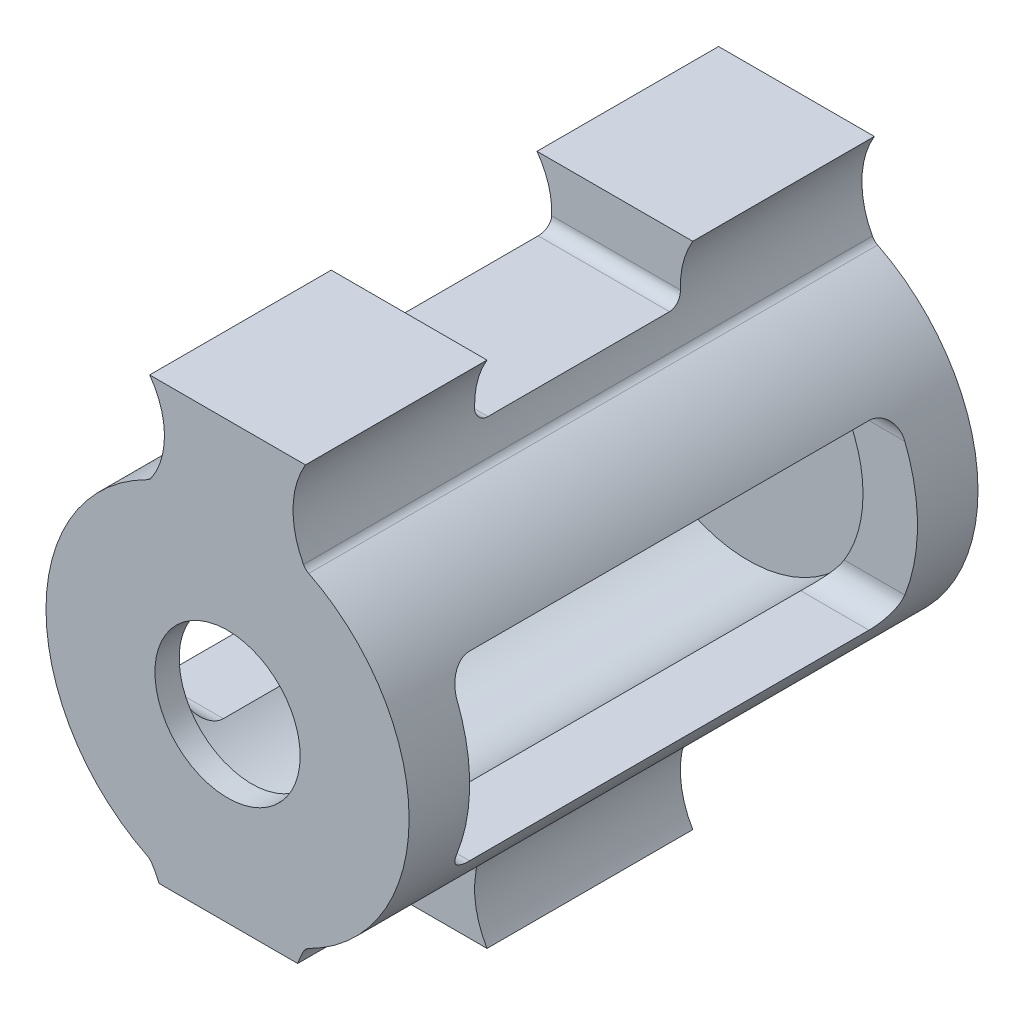
SolidWorks part; units mm, degrees
material "AISI 4130 Steel, annealed at 865C"
ref_plane "Front Plane" through (0, 0, 0) normal (0, 0, 1) x (1, 0, 0)
ref_plane "Top Plane" through (0, 0, 0) normal (0, 1, 0) x (1, 0, 0)
ref_plane "Right Plane" through (0, 0, 0) normal (1, 0, 0) x (0, 0, -1)
other "Center of Mass"
sketch "Sketch1" plane through (0, 0, 0) normal (0, 0, 1) x (1, 0, 0)
  line L8 (-38.1, 0) -> (-52.5688, 0)
  line L9 (-16.3476, 53.4646) -> (16.3476, 53.4646)
  line L10 (-16.3476, -53.4646) -> (16.3476, -53.4646)
  circle A0 centre (0, 0) radius 38.1
  circle A1 centre (0, 0) radius 26.67
  arc A2 (-16.3476, 53.4646) -> (-16.3476, 34.4146) centre (-29.4008, 43.9396) cw
  arc A3 (16.3476, 53.4646) -> (16.3476, 34.4146) centre (32.4071, 43.9396) ccw
  arc A4 (16.3476, -53.4646) -> (16.3476, -34.4146) centre (32.4071, -43.9396) cw
  arc A5 (-16.3476, -53.4646) -> (-16.3476, -34.4146) centre (-29.4008, -43.9396) ccw
  point P9 (0, 53.4646)
  dimension "D1" = 76.2
  dimension "D3" = 19.05
  dimension "D2" = 11.43
extrude "Boss-Extrude1" add sketch "Sketch1" along normal blind 114.3 and the other way blind 5.08 contours A3 L9 A2 A0 | A0 A1 | A5 L10 A4 A0 region at (0.1985, 45.335, 0) region at (0, 37.0224, 0) region at (0.1985, -45.335, 0)
ref_plane "Plane2" through (-16.3476, 0, 0) normal (1, 0, 0) x (0, 0, -1)
sketch "Sketch3" plane through (-16.3476, 0, 0) normal (1, 0, 0) x (0, 0, -1)
  line L5 (-33.02, 53.4646) -> (-33.02, 40.7646)
  line L6 (-33.02, 53.4646) -> (-76.2, 53.4646)
  line L7 (-33.02, 40.7646) -> (-76.2, 40.7646)
  line L8 (-76.2, 53.4646) -> (-76.2, 40.7646)
  line L9 (-114.3, 53.4646) -> (5.08, 53.4646) construction
  line L10 (-114.3, 34.4146) -> (5.08, 34.4146) construction
  line L11 (-76.2, -37.9706) -> (-114.3, -37.9706)
  line L12 (-114.3, -34.4146) -> (-114.3, -53.4646) construction
  line L13 (-114.3, -37.9706) -> (-114.3, -53.4646)
  line L14 (-114.3, -53.4646) -> (-76.2, -53.4646)
  line L15 (-114.3, -53.4646) -> (5.08, -53.4646) construction
  line L16 (-76.2, -53.4646) -> (-76.2, -37.9706)
  line L17 (-114.3, -34.4146) -> (5.08, -34.4146) construction
  line L18 (-54.61, 53.4646) -> (-54.61, 62.3768)
  line L19 (5.08, -37.9706) -> (5.08, -53.4646)
  line L20 (5.08, -53.4646) -> (-33.02, -53.4646)
  line L21 (-33.02, -53.4646) -> (-33.02, -37.9706)
  line L22 (-33.02, -37.9706) -> (5.08, -37.9706)
  dimension "D1" = 38.1
  dimension "D2" = 38.1
  dimension "D3" = 12.7
  dimension "D4" = 6.35
  dimension "D5" = 3.556
  dimension "D6" = 38.1
extrude "Cut-Extrude1" cut sketch "Sketch3" against normal through all both and the other way through all contours L6 L8 L7 L5 | L14 L16 L11 L13 | L22 L21 L20 L19 region at (-16.3476, 47.1146, 54.61) region at (-16.3476, -45.7176, 95.25) region at (-16.3476, -45.7176, 13.97)
fillet "Fillet1" radius 2.54 4 edges at (0.2252, 40.7646, 33.02) (0.2252, 40.7646, 76.2) (0.1652, -37.9706, 76.2) (0.1652, -37.9706, 33.02)
fillet "Fillet2" radius 2.54 4 edges at (-16.3476, 34.4146, 54.61) (16.3476, 34.4146, 54.61) (16.3476, -34.4146, 54.61) (-16.3476, -34.4146, 54.61)
sketch "Sketch5" plane through (-16.3476, 0, 0) normal (1, 0, 0) x (0, 0, -1)
  line L0 (-101.6, 19.05) -> (-101.6, -19.05)
  line L1 (-101.6, 19.05) -> (-7.62, 19.05)
  line L2 (-101.6, -19.05) -> (-7.62, -19.05)
  line L3 (-7.62, 19.05) -> (-7.62, -19.05)
  line L4 (-114.3, 34.0791) -> (-114.3, -34.0791) construction
  line L5 (5.08, -34.0791) -> (5.08, 34.0791) construction
  point P0 (-7.62, 0)
  dimension "D1" = 12.7
  dimension "D2" = 38.1
  dimension "D3" = 12.7
extrude "Cut-Extrude2" cut sketch "Sketch5" against normal through all both and the other way through all
fillet "Fillet3" radius 5.08 7 edges at (25.8303, 19.05, 7.62) (25.8303, 19.05, 101.6) (25.8303, -19.05, 7.62) (25.8303, -19.05, 101.6) (-25.8303, -19.05, 101.6) (-25.8303, -19.05, 7.62) (-25.8303, 19.05, 7.62)
sketch "Sketch6" plane through (0, 0, -5.08) normal (0, 0, -1) x (-1, 0, 0)
  circle A0 centre (0, 0) radius 26.67 construction
  circle A1 centre (0, 0) radius 26.67
  circle A2 centre (0, 0) radius 5.08
  dimension "D1" = 10.16
extrude "Boss-Extrude2" add sketch "Sketch6" against normal blind 10.16
sketch "Sketch7" plane through (0, 0, 114.3) normal (0, 0, 1) x (1, 0, 0)
  circle A0 centre (0, 0) radius 26.67 construction
  circle A1 centre (0, 0) radius 26.67
  circle A2 centre (0, 0) radius 15.24
  dimension "D1" = 30.48
extrude "Boss-Extrude3" add sketch "Sketch7" against normal blind 5.08
